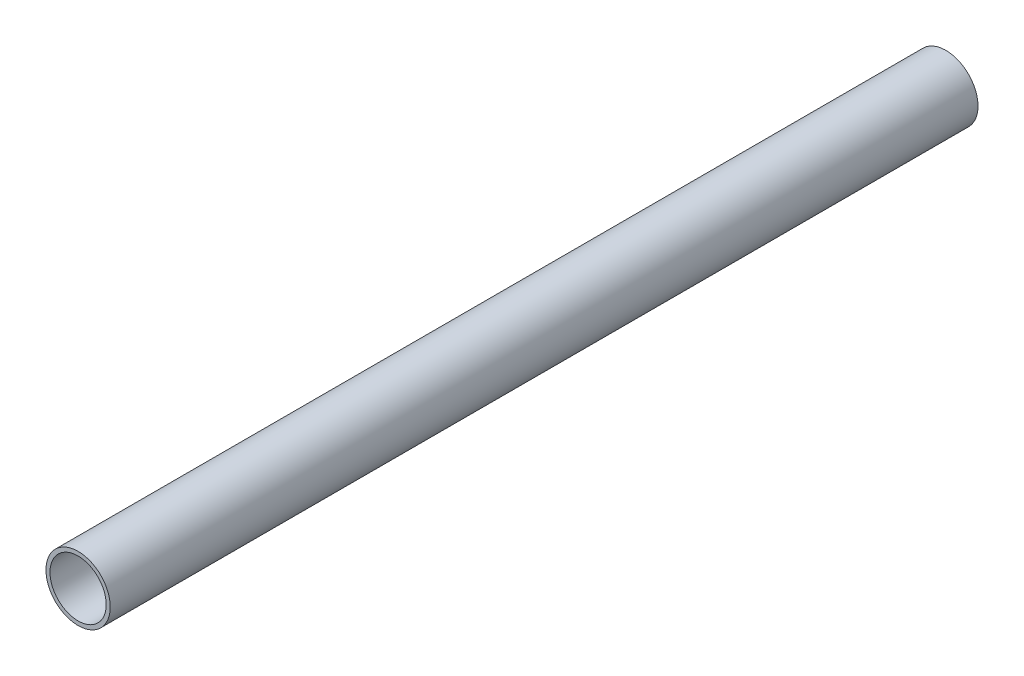
SolidWorks part; units mm, degrees
material "PC High Viscosity"
ref_plane "Front Plane" through (0, 0, 0) normal (0, 0, 1) x (1, 0, 0)
ref_plane "Top Plane" through (0, 0, 0) normal (0, 1, 0) x (1, 0, 0)
ref_plane "Right Plane" through (0, 0, 0) normal (1, 0, 0) x (0, 0, -1)
sketch "Sketch1" plane through (0, 0, 0) normal (0, 0, 1) x (1, 0, 0)
  circle A0 centre (0, 0) radius 12.7
  circle A1 centre (0, 0) radius 11.1125
  dimension "D1" = 25.4
  dimension "D2" = 1.5875
extrude "Boss-Extrude1" add sketch "Sketch1" along normal blind 342.74
